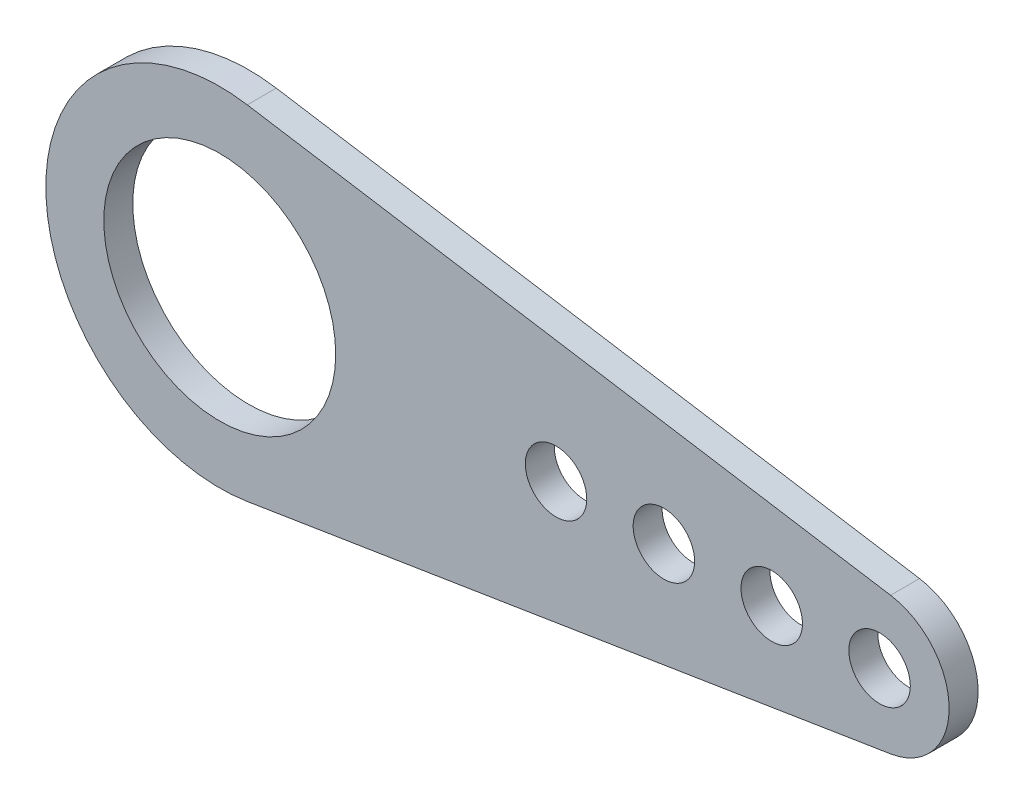
SolidWorks part; units mm, degrees
material "Custom Plastic"
ref_plane "X-Y Datum" through (0, 0, 0) normal (0, 0, 1) x (1, 0, 0)
ref_plane "X-Z Datum" through (0, 0, 0) normal (0, 1, 0) x (1, 0, 0)
ref_plane "Y-Z Datum" through (0, 0, 0) normal (1, 0, 0) x (0, 0, -1)
sketch "Flat sketch" plane through (0, 0, 0) normal (0, 0, 1) x (1, 0, 0)
  line L0 (-12.7, 0) -> (72.263, 0) construction
  line L2 (3.0132, 18.8102) -> (73.4683, 7.5241)
  line L3 (3.0132, -18.8102) -> (73.4683, -7.5241)
  line L4 (73.4683, 7.5241) -> (73.4683, -7.5241) construction
  circle A0 centre (0, 0) radius 12.7
  circle A1 centre (0, 0) radius 19.05
  circle A2 centre (72.263, 0) radius 3.3655
  circle A8 centre (72.263, 0) radius 7.62
  circle A9 centre (60.452, 0) radius 3.3655
  circle A10 centre (48.641, 0) radius 3.3655
  circle A11 centre (36.83, 0) radius 3.3655
  point P5 (12.7, 0)
  point P9 (19.05, 0)
  dimension "D1" = 25.4
  dimension "D2" = 38.1
  dimension "D3" = 6.731
  dimension "D7" = 15.24
  dimension "D5" = 17.78
  dimension "D6" = 11.811
  dimension "D4" = 4
extrude "Extrude face" add sketch "Flat sketch" along normal blind 3.175 contours A1 A0 | A8 A2 | A11 | A10 | A9 | A2 | A8 L2 A1 L3 A11 A10 A9 region at (38.1144, 12.3785, 0) region at (14.0866, 12.0097, 0) region at (77.8976, 4.8039, 0) region at (72.263, 0, 0) region at (60.452, 0, 0) region at (48.641, 0, 0) region at (36.83, 0, 0)
extrude "Extrude cut - holes" cut sketch "Flat sketch<4>" along normal up to surface (3.175 mm away) contours A11 | A10 | A9 | A2 region at (72.263, 0, 0) region at (60.452, 0, 0) region at (48.641, 0, 0) region at (36.83, 0, 0) up to face at (12.7, 0, 3.175)
sketch "Flat sketch<4>" plane through (0, 0, 0) normal (0, 0, 1) x (1, 0, 0) same geometry as "Flat sketch"
equation "\"Torsion Bar O.D.\"= 1in"
equation "\"Lever I.D. Torsion O.D. Clearance\"= 0"
equation "\"Lever I.D.\"= \"Torsion Bar O.D.\" + \"Lever I.D. Torsion O.D. Clearance\""
equation "\"D1@Flat sketch\" = \"Lever I.D.\""
equation "\"Lever O.D.\"= 1.5"
equation "\"D2@Flat sketch\" = \"Lever O.D.\""
equation "\"Lever Rod end I.D.\"= 0.265"
equation "\"D3@Flat sketch\" = \"Lever Rod end I.D.\""
equation "\"Distance b/w Lever Rod end holes\"= 0"
equation "\"Number of Lever Rod end holes\"= 0"
equation "\"Lever arc radius\"= 0.5"
equation "\"Lever rod end hole and Lever O.D. clearance\"= 0.7"
equation "\"Lever thickness\"= 1 / 8in"
equation "\"D1@Extrude face\" = \"Lever thickness\""
equation "\"D5@Flat sketch\"=\"Lever rod end hole and Lever O.D. clearance\""
